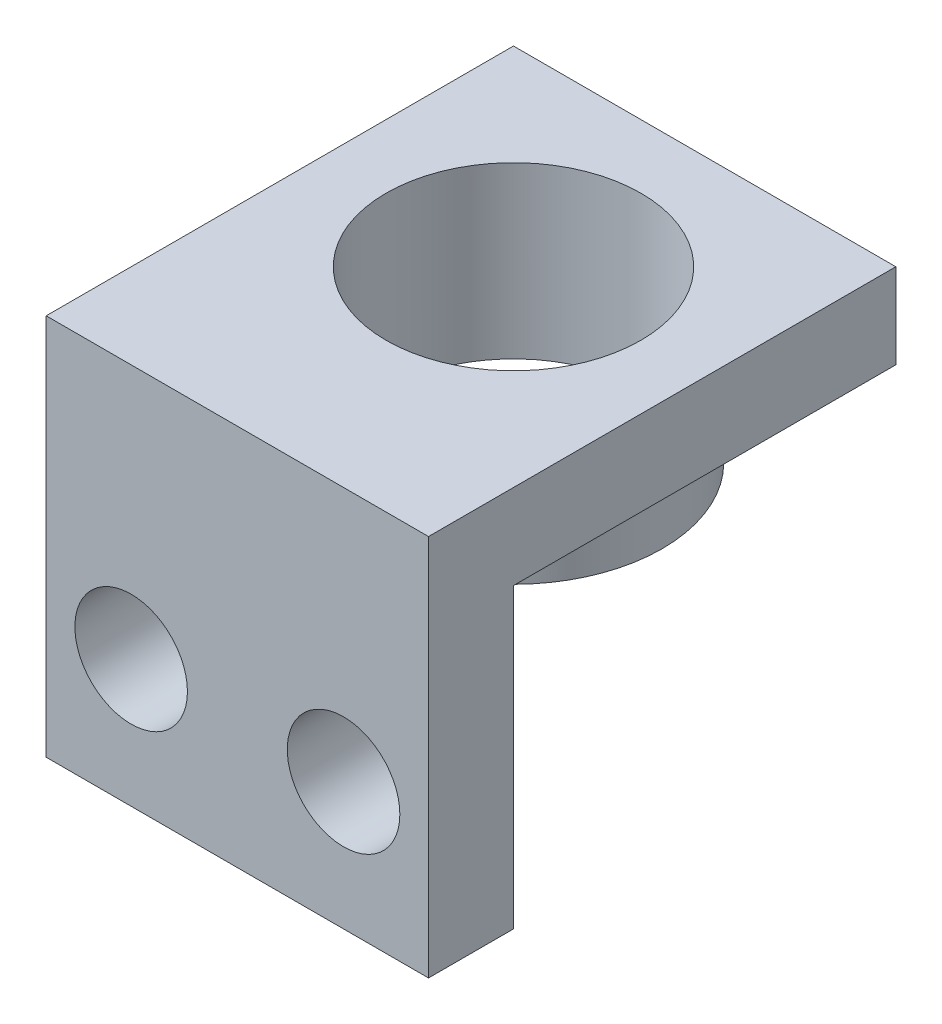
SolidWorks part; units mm, degrees
ref_plane "Front Plane" through (0, 0, 0) normal (0, 0, 1) x (1, 0, 0)
ref_plane "Top Plane" through (0, 0, 0) normal (0, 1, 0) x (1, 0, 0)
ref_plane "Right Plane" through (0, 0, 0) normal (1, 0, 0) x (0, 0, -1)
sketch "Sketch1" plane through (0, 0, 0) normal (0, 1, 0) x (1, 0, 0)
  line L0 (9, 18) -> (9, 0) construction
  line L1 (0, 0) -> (18, 0)
  line L2 (0, 0) -> (0, 18)
  line L3 (0, 18) -> (18, 18)
  line L4 (18, 0) -> (18, 18)
  line L5 (0, 9) -> (18, 9) construction
  circle A0 centre (9, 9) radius 6
  dimension "D1" = 12
  dimension "D2" = 18
  dimension "D3" = 18
extrude "Boss-Extrude1" add sketch "Sketch1" along normal blind 4
sketch "Sketch2" plane through (0, 0, 0) normal (0, 0, 1) x (1, 0, 0)
  line L0 (18, 4) -> (18, 0) construction
  line L1 (0, 4) -> (18, 4)
  line L2 (0, 4) -> (0, -14)
  line L3 (0, -14) -> (18, -14)
  line L4 (18, 4) -> (18, -14)
  line L5 (0, -8) -> (18, -8) construction
  circle A0 centre (4, -8) radius 2.65
  circle A1 centre (14, -8) radius 2.65
  dimension "D2" = 5.3
  dimension "D1" = 18
  dimension "D3" = 10
  dimension "D4" = 4
  dimension "D5" = 6
extrude "Boss-Extrude2" add sketch "Sketch2" along normal blind 4
sketch "Sketch3" plane through (0, 0, 0) normal (0, -1, 0) x (1, 0, 0)
  circle A1 centre (9, -9) radius 7
  circle A2 centre (9, -9) radius 6 construction
  circle A3 centre (9, -9) radius 6
  dimension "D1" = 14
extrude "Boss-Extrude3" add sketch "Sketch3" along normal blind 4
